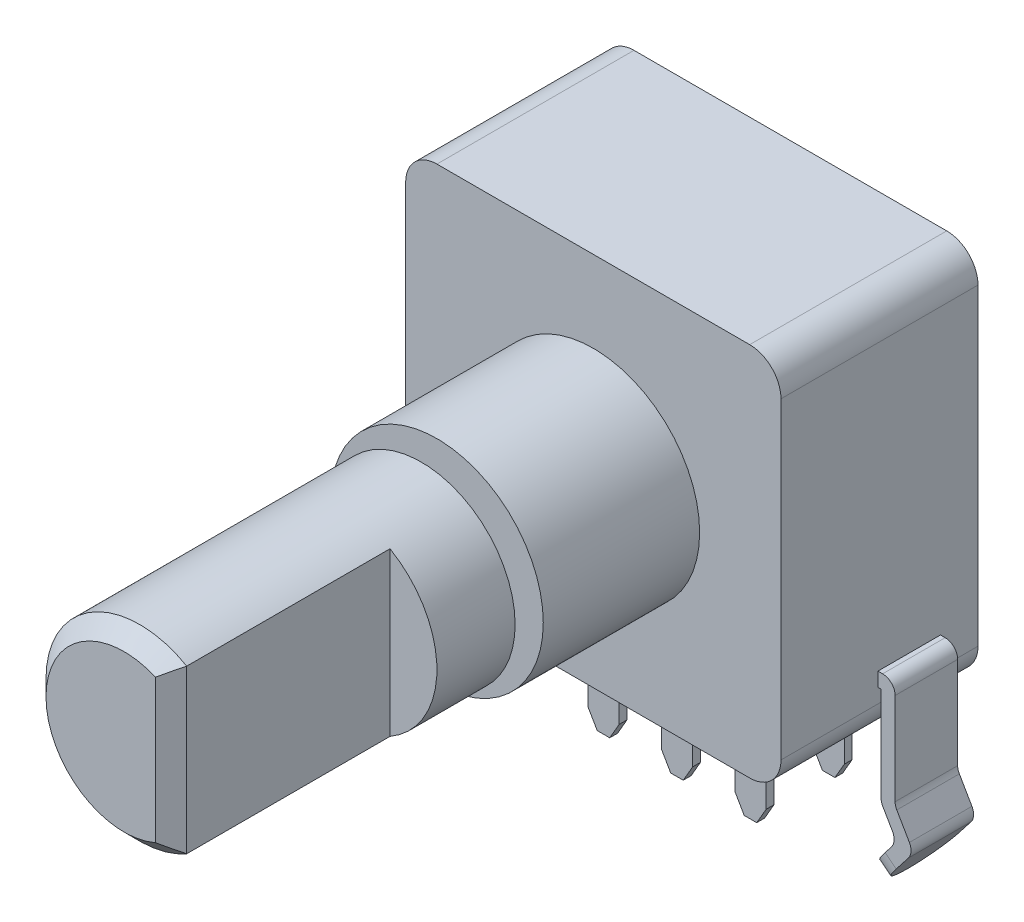
SolidWorks part; units mm, degrees
note: The reader was unsure of these and kept them because the rebuilt part matched: shared geometry of "Esquisse3<4>".
ref_plane "Plan de face" through (0, 0, 0) normal (0, 0, 1) x (1, 0, 0)
ref_plane "Plan de dessus" through (0, 0, 0) normal (0, 1, 0) x (1, 0, 0)
ref_plane "Plan de droite" through (0, 0, 0) normal (1, 0, 0) x (0, 0, -1)
sketch "Esquisse1" plane through (0, 0, 0) normal (0, 0, 1) x (1, 0, 0)
  line L1 (-6, 6) -> (6, 6)
  line L2 (-6, 6) -> (-6, -6)
  line L3 (-6, -6) -> (6, -6)
  line L4 (6, 6) -> (6, -6)
  line L5 (-6, 6) -> (6, -6) construction
  line L6 (-6, -6) -> (6, 6) construction
  point P0 (0, 0)
  dimension "D1" = 12
extrude "Boss.-Extru.1" add sketch "Esquisse1" along normal blind 6.3
sketch "Esquisse2" plane through (0, 0, 6.3) normal (0, 0, 1) x (1, 0, 0)
  circle A0 centre (0, 0) radius 3.4
  dimension "D1" = 6.8
extrude "Boss.-Extru.2" add sketch "Esquisse2" along normal blind 5
sketch "Esquisse5" plane through (0, 0, 11.3) normal (0, 0, 1) x (1, 0, 0)
  circle A0 centre (0, 0) radius 1.8
  dimension "D1" = 3.6
extrude "Boss.-Extru.5" add sketch "Esquisse5" along normal blind 0.5
sketch "Esquisse3" plane through (0, 0, 11.8) normal (0, 0, 1) x (1, 0, 0)
  line L0 (1.5, 2.5981) -> (1.5, -2.5981)
  circle A0 centre (0, 0) radius 3
  circle M4 centre (0, 0) radius 1.8
  dimension "D1" = 6
  dimension "D2" = 4.5
extrude "Boss.-Extru.3" add sketch "Esquisse3" along normal blind 2.5 contours A0
extrude "Boss.-Extru.6" add sketch "Esquisse3<4>" along normal offset from surface (7 mm away) 15 from surface at 2.5 contours L0 A0 M4 | L0 M4
sketch "Esquisse3<4>" plane through (0, 0, 11.8) normal (0, 0, 1) x (1, 0, 0) same geometry as "Esquisse3"
sketch "Esquisse4" plane through (0, -6, 0) normal (0, -1, 0) x (1, 0, 0)
  line L0 (-2.35, 3.5) -> (0, 3.5) construction
  line L1 (-0.5, 3.625) -> (0.5, 3.625)
  line L2 (-0.5, 3.625) -> (-0.5, 3.375)
  line L3 (-0.5, 3.375) -> (0.5, 3.375)
  line L4 (0.5, 3.625) -> (0.5, 3.375)
  line L5 (-0.5, 3.625) -> (0.5, 3.375) construction
  line L6 (-0.5, 3.375) -> (0.5, 3.625) construction
  line L7 (1.85, 3.625) -> (2.85, 3.625)
  line L8 (1.85, 3.625) -> (1.85, 3.375)
  line L9 (1.85, 3.375) -> (2.85, 3.375)
  line L10 (2.85, 3.625) -> (2.85, 3.375)
  line L11 (1.85, 3.625) -> (2.85, 3.375) construction
  line L12 (1.85, 3.375) -> (2.85, 3.625) construction
  line L13 (-2.85, 3.625) -> (-1.85, 3.625)
  line L14 (-2.85, 3.625) -> (-2.85, 3.375)
  line L15 (-2.85, 3.375) -> (-1.85, 3.375)
  line L16 (-1.85, 3.625) -> (-1.85, 3.375)
  line L17 (-2.85, 3.625) -> (-1.85, 3.375) construction
  line L18 (-2.85, 3.375) -> (-1.85, 3.625) construction
  line L19 (-2.85, 1.125) -> (-1.85, 1.125)
  line L20 (-2.85, 1.125) -> (-2.85, 0.875)
  line L21 (-2.85, 0.875) -> (-1.85, 0.875)
  line L22 (-1.85, 1.125) -> (-1.85, 0.875)
  line L23 (-2.85, 1.125) -> (-1.85, 0.875) construction
  line L24 (-2.85, 0.875) -> (-1.85, 1.125) construction
  line L25 (1.85, 1.125) -> (2.85, 1.125)
  line L26 (1.85, 1.125) -> (1.85, 0.875)
  line L27 (1.85, 0.875) -> (2.85, 0.875)
  line L28 (2.85, 1.125) -> (2.85, 0.875)
  line L29 (1.85, 1.125) -> (2.85, 0.875) construction
  line L30 (1.85, 0.875) -> (2.85, 1.125) construction
  line L31 (0, 3.5) -> (2.35, 3.5) construction
  line L32 (-6, 0) -> (6, 0) construction
  point P0 (0, 3.5)
  point P5 (2.35, 3.5)
  point P10 (-2.35, 3.5)
  point P15 (-2.35, 1)
  point P20 (2.35, 1)
  dimension "D1" = 1
  dimension "D2" = 0.25
  dimension "D3" = 2.35
  dimension "D4" = 2.5
  dimension "D5" = 1
extrude "Boss.-Extru.4" add sketch "Esquisse4" along normal blind 3.8
chamfer "Chanfrein1" distance 0.5 angle 45 2 edges at (1.5, 0, 21.3) (-3, 0, 21.3)
fillet "Congé1" radius 1 4 edges at (6, -6, 3.15) (6, 6, 3.15) (-6, -6, 3.15) (-6, 6, 3.15)
chamfer "Chanfrein2" distance 0.3 angle 60 20 edges at (1.85, -6, 1) (2.85, -6, 1) (2.85, -6, 3.5) (1.85, -6, 3.5) (0.5, -6, 3.5) (-0.5, -6, 3.5) (-1.85, -6, 3.5) (-2.85, -6, 3.5) (-2.85, -6, 1) (-1.85, -6, 1) (-2.85, -9.8, 1) (-1.85, -9.8, 1) (-2.85, -9.8, 3.5) (-1.85, -9.8, 3.5) (-0.5, -9.8, 3.5) (0.5, -9.8, 3.5) (1.85, -9.8, 3.5) (2.85, -9.8, 3.5) (1.85, -9.8, 1) (2.85, -9.8, 1)
sketch "Esquisse6" plane through (0, 0, 0) normal (0, 0, -1) x (-1, 0, 0)
  line L0 (-5.6257, -0.6041) -> (6.0743, -0.6041) construction
  line L1 (-6, -4.0901) -> (-6.15, -4.0901)
  line L2 (-6, -5) -> (-6, 5) construction
  line L3 (-6.55, -4.4901) -> (-6.55, -7.433)
  line L4 (-6.6036, -7.633) -> (-7.0066, -8.331)
  line L5 (-6.9754, -8.7772) -> (-5.9695, -10.0646)
  line L6 (-5.9695, -10.0646) -> (-5.6149, -9.7876)
  line L7 (-5.6149, -9.7876) -> (-6.4339, -8.7394)
  line L8 (-6.4651, -8.2931) -> (-6.1536, -7.7535)
  line L9 (-6.1, -7.5535) -> (-6.1, -4.5401)
  line L10 (-6.1, -4.5401) -> (-6, -4.5401)
  line L11 (-6, -4.5401) -> (-6, -4.0901)
  line L12 (-6.8051, -7.982) -> (-6.4154, -8.207) construction
  line L13 (-6, -5) -> (-6, 5) construction
  line L14 (-6.1, -4.5401) -> (-6.55, -4.5401) construction
  arc A0 (-7.0066, -8.331) -> (-6.9754, -8.7772) centre (-6.6602, -8.531) ccw
  arc A1 (-6.4339, -8.7394) -> (-6.4651, -8.2931) centre (-6.1187, -8.4931) cw
  arc A2 (-6.1536, -7.7535) -> (-6.1, -7.5535) centre (-6.5, -7.5535) ccw
  arc A3 (-6.55, -7.433) -> (-6.6036, -7.633) centre (-6.95, -7.433) cw
  arc A4 (-6.15, -4.0901) -> (-6.55, -4.4901) centre (-6.15, -4.4901) ccw
  point P16 (-6.093, -4.5401)
  point P17 (-5.6328, -9.8421)
  point P20 (-6.55, -7.5381)
  point P26 (-6.6, -8.5268)
  point P29 (-6.1, -7.6607)
  point P32 (-6.55, -7.5401)
  point P35 (-6.55, -4.0901)
  dimension "D9" = 0.4
  dimension "D1" = 11.7
  dimension "D2" = 0.45
  dimension "D3" = 0.1
  dimension "D4" = 3.45
  dimension "D5" = 150
  dimension "D6" = 112
  dimension "D7" = 1
  dimension "D8" = 1.6
extrude "Boss.-Extru.7" add sketch "Esquisse6" against normal blind 2 from offset 1.2 offset against normal yes
fillet "Congé2" radius 1 2 edges at (5.7922, -9.9261, 1.2) (5.7922, -9.9261, 3.2)
mirror "Symétrie1" about plane through (0, 0, 0) normal (1, 0, 0) of "Congé2", "Boss.-Extru.7"
